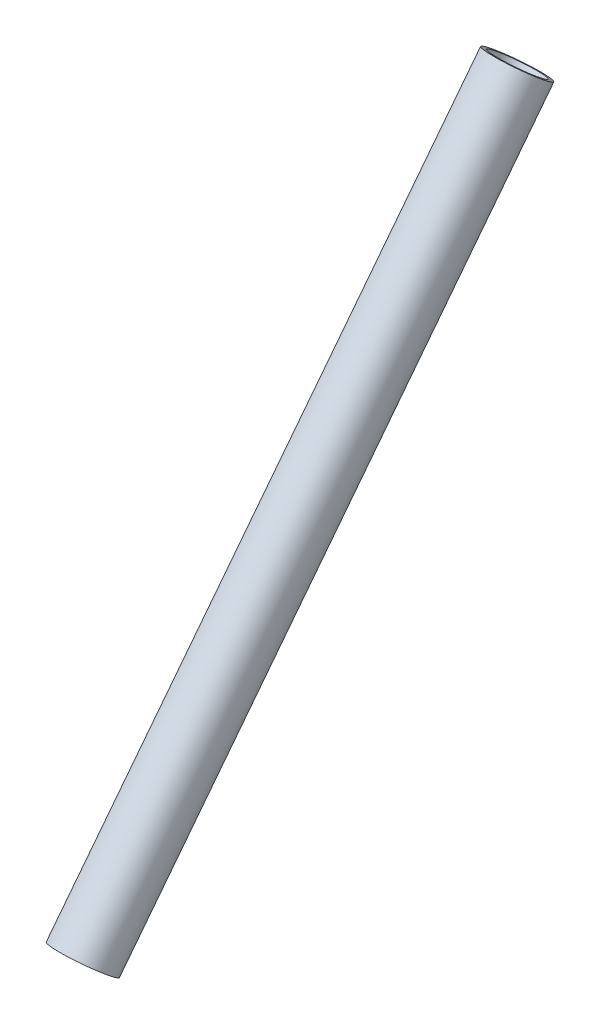
SolidWorks part; units mm, degrees
ref_plane "Front Plane" through (0, 0, 0) normal (0, 0, 1) x (1, 0, 0)
ref_plane "Top Plane" through (0, 0, 0) normal (0, 1, 0) x (1, 0, 0)
ref_plane "Right Plane" through (0, 0, 0) normal (1, 0, 0) x (0, 0, -1)
sketch3d "3DSketch1"
  line L0 (709.53, 528.41, 34.08) -> (709.53, 335.03, 184.5) construction
  line L1 (709.53, 493.285, 61.4019) -> (709.53, 370.155, 157.1781)
  point P0 (709.53, 335.03, 184.5)
  point P2 (709.53, 528.41, 34.08)
  dimension "D1" = 44.5
  dimension "D2" = 44.5
sweep "Sweep-Thin1" add path "3DSketch1" circular profile diameter 12.7 parameters "D1"=1, "D3"=12.7
